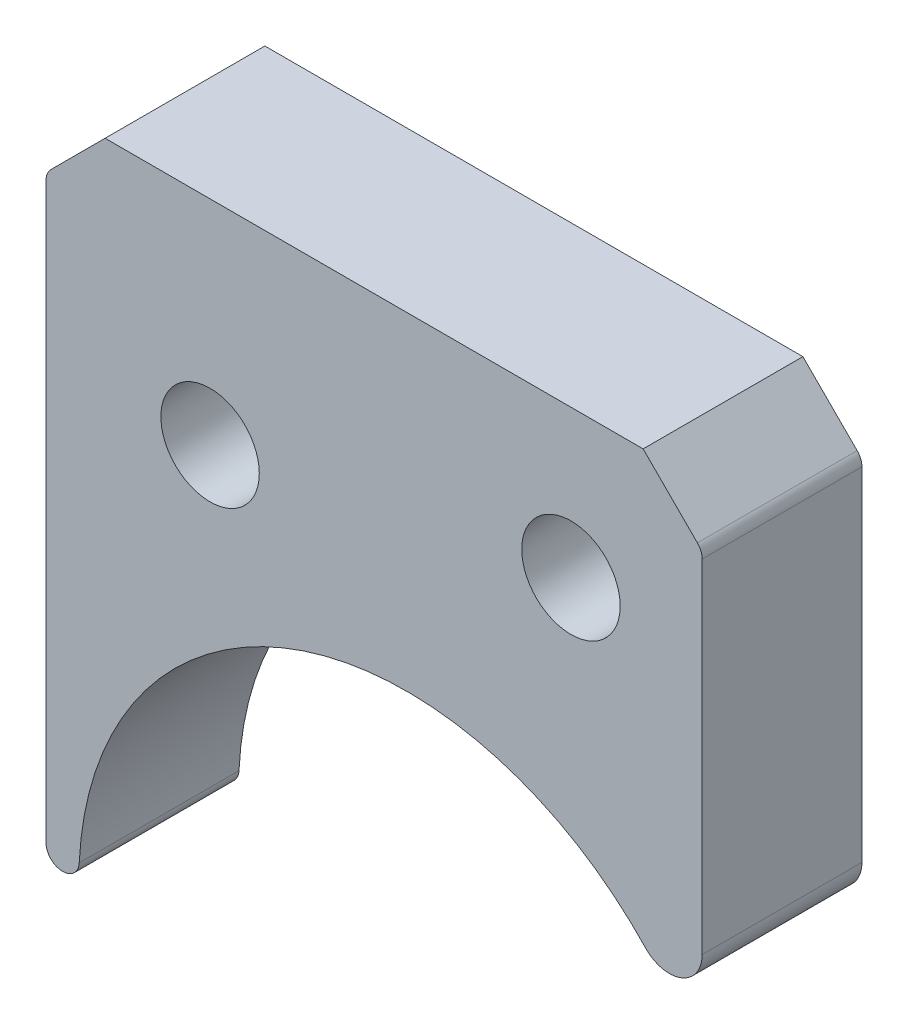
SolidWorks part; units mm, degrees
ref_plane "Front Plane" through (0, 0, 0) normal (0, 0, 1) x (1, 0, 0)
ref_plane "Top Plane" through (0, 0, 0) normal (0, 1, 0) x (1, 0, 0)
ref_plane "Right Plane" through (0, 0, 0) normal (1, 0, 0) x (0, 0, -1)
sketch "Sketch1" plane through (0, 0, 0) normal (0, 0, 1) x (1, 0, 0)
  line L1 (0, 0) -> (1, 0)
  line L2 (0, 0) -> (0, 20)
  line L3 (0, 20) -> (20, 20)
  line L4 (20, 4.3589) -> (20, 20)
  arc A0 (20, 4.3589) -> (1, 0) centre (11, 0) ccw
extrude "Boss-Extrude1" add sketch "Sketch1" along normal blind 4.87
sketch "Sketch2" plane through (0, 0, 4.87) normal (0, 0, 1) x (1, 0, 0)
  line L0 (5, 15.5) -> (11, 15.5) construction
  line L1 (11, 15.5) -> (16, 15.5) construction
  line L2 (11, 15.5) -> (11, 0) construction
  line L3 (5, 15.5) -> (5, 13.5) construction
  circle A0 centre (5, 13.5) radius 1.5
  circle A1 centre (16, 15.5) radius 1.5
  point P7 (0, 0)
  point P10 (0, 0)
  point P11 (15, 15.5)
  point P12 (15, 15.5)
  point P13 (0, 0)
  point P14 (0, 0)
  dimension "D5" = 15.5
  dimension "D4" = 3
  dimension "D1" = 11
  dimension "D2" = 6
  dimension "D3" = 2
  dimension "D6" = 5
extrude "Cut-Extrude1" cut sketch "Sketch2" against normal blind 4.87
chamfer "Chamfer1" distance 1.8 angle 45 2 edges at (0, 20, 2.435) (20, 20, 2.435)
fillet "Fillet1" radius 0.5 4 edges at (0, 0, 2.435) (1, 0, 2.435) (20, 18.2, 2.435) (0, 18.2, 2.435)
fillet "Fillet2" radius 1 1 edges at (20, 4.3589, 2.435)
